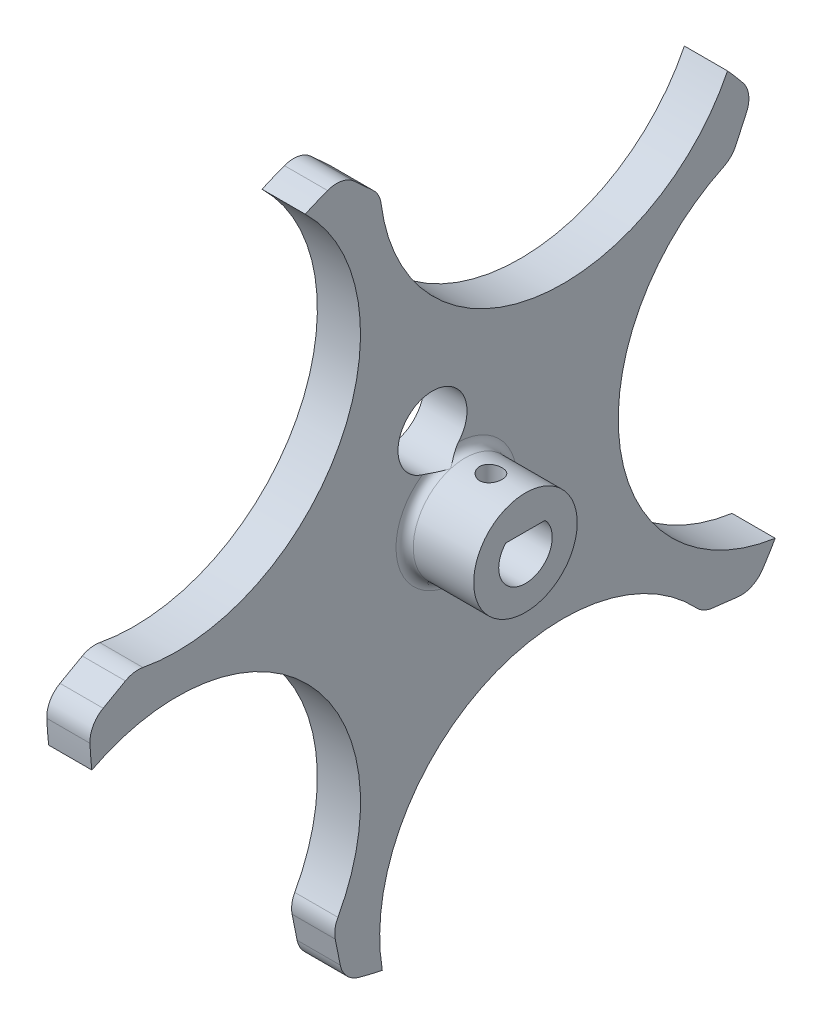
SolidWorks part; units mm, degrees
material "ABS"
ref_plane "前视基准面" through (0, 0, 0) normal (0, 0, 1) x (1, 0, 0)
ref_plane "上视基准面" through (0, 0, 0) normal (0, 1, 0) x (1, 0, 0)
ref_plane "右视基准面" through (0, 0, 0) normal (1, 0, 0) x (0, 0, -1)
ref_plane "基准面1" through (-38.0916, 0, 0) normal (-1, 0, 0) x (0, 0, 1)
sketch "草图2" plane through (-38.0916, 0, 0) normal (-1, 0, 0) x (0, 0, 1)
  line L8 (50.9114, 23.5166) -> (55.2476, 27.5126)
  line L9 (42.0845, -12.8976) -> (18.6016, -26.2672) construction
  line L10 (22.1126, 5.3045) -> (42.0845, -12.8976) construction
  line L11 (10.1802, 6.7498) -> (7.7198, 12.1087)
  line L12 (42.0845, -12.8976) -> (22.1126, 5.3045) construction
  line L13 (23.3345, -12.8976) -> (42.0845, -12.8976) construction
  line L14 (53.2241, 11.7215) -> (42.0845, -12.8976) construction
  line L15 (36.2904, 4.9347) -> (42.0845, -12.8976) construction
  line L16 (79.4441, -10.0398) -> (84.5845, -12.929)
  line L17 (42.0845, -12.8976) -> (53.2241, 11.7215) construction
  line L18 (68.941, -15.8842) -> (42.0845, -12.8976) construction
  line L19 (57.2536, -1.8766) -> (42.0845, -12.8976) construction
  line L20 (56.3471, -47.5456) -> (55.1878, -53.3272)
  line L21 (42.0845, -12.8976) -> (68.941, -15.8842) construction
  line L22 (47.5432, -39.3626) -> (42.0845, -12.8976) construction
  line L23 (57.2536, -23.9186) -> (42.0845, -12.8976) construction
  line L24 (13.5397, -37.169) -> (7.6828, -37.853)
  line L25 (42.0845, -12.8976) -> (47.5432, -39.3626) construction
  line L26 (18.6016, -26.2672) -> (42.0845, -12.8976) construction
  line L27 (36.2904, -30.7299) -> (42.0845, -12.8976) construction
  arc A41 (55.2476, 27.5126) -> (59.6047, 25.8231) centre (42.0845, -12.8976) cw
  arc A43 (7.7198, 12.1087) -> (10.673, 15.7305) centre (42.0845, -12.8976) cw
  arc A45 (10.1802, 6.7498) -> (5.1509, -33.9252) centre (2.0845, -12.8976) cw
  arc A46 (50.9114, 23.5166) -> (10.673, 15.7305) centre (29.7238, 25.1447) cw
  arc A47 (84.5845, -12.929) -> (84.3241, -17.5949) centre (42.0845, -12.8976) cw
  arc A49 (79.4441, -10.0398) -> (59.6047, 25.8231) centre (74.4452, 10.6138) cw
  arc A50 (55.1878, -53.3272) -> (50.6698, -54.5214) centre (42.0845, -12.8976) cw
  arc A52 (56.3471, -47.5456) -> (84.3241, -17.5949) centre (74.4452, -36.409) cw
  arc A53 (7.6828, -37.853) -> (5.1509, -33.9252) centre (42.0845, -12.8976) cw
  arc A55 (13.5397, -37.169) -> (50.6698, -54.5214) centre (29.7238, -50.9399) cw
  point P15 (42.0845, -12.8976)
  point P16 (42.0845, -12.8976)
  point P18 (42.0845, -12.8976)
  point P19 (42.0845, -12.8976)
  point P23 (42.0845, -12.8976)
  point P24 (42.0845, -12.8976)
  point P27 (42.0845, -12.8976)
  point P28 (42.0845, -12.8976)
  point P29 (42.0845, -12.8976)
  point P30 (42.0845, -12.8976)
  point P31 (42.0845, -12.8976)
  point P32 (42.0845, -12.8976)
  point P33 (42.0845, -12.8976)
  point P34 (42.0845, -12.8976)
  point P35 (42.0845, -12.8976)
  point P36 (42.0845, -12.8976)
  point P37 (42.0845, -12.8976)
  point P38 (42.0845, -12.8976)
  point P39 (42.0845, -12.8976)
  point P40 (42.0845, -12.8976)
  point P41 (42.0845, -12.8976)
  point P42 (42.0845, -12.8976)
  point P44 (42.0845, -12.8976)
  point P45 (42.0845, -12.8976)
  point P46 (42.0845, -12.8976)
  point P47 (42.0845, -12.8976)
  point P48 (42.0845, -12.8976)
  point P49 (42.0845, -12.8976)
  point P50 (42.0845, -12.8976)
  point P51 (42.0845, -12.8976)
  point P52 (42.0845, -12.8976)
  point P53 (42.0845, -12.8976)
  point P62 (42.0845, -12.8976)
  point P63 (42.0845, -12.8976)
  point P64 (42.0845, -12.8976)
  point P65 (42.0845, -12.8976)
  point P66 (42.0845, -12.8976)
  point P67 (42.0845, -12.8976)
  point P69 (42.0845, -12.8976)
  point P70 (42.0845, -12.8976)
  point P71 (42.0845, -12.8976)
  point P72 (42.0845, -12.8976)
  point P73 (42.0845, -12.8976)
  point P74 (42.0845, -12.8976)
  point P75 (42.0845, -12.8976)
  point P76 (42.0845, -12.8976)
  point P77 (42.0845, -12.8976)
  point P78 (42.0845, -12.8976)
  point P87 (42.0845, -12.8976)
  point P88 (42.0845, -12.8976)
  point P89 (42.0845, -12.8976)
  point P90 (42.0845, -12.8976)
  point P91 (42.0845, -12.8976)
  point P92 (42.0845, -12.8976)
  point P94 (42.0845, -12.8976)
  point P95 (42.0845, -12.8976)
  point P96 (42.0845, -12.8976)
  point P97 (42.0845, -12.8976)
  point P98 (42.0845, -12.8976)
  point P99 (42.0845, -12.8976)
  point P100 (42.0845, -12.8976)
  point P101 (42.0845, -12.8976)
  point P102 (42.0845, -12.8976)
  point P103 (42.0845, -12.8976)
  point P112 (42.0845, -12.8976)
  point P113 (42.0845, -12.8976)
  point P114 (42.0845, -12.8976)
  point P115 (42.0845, -12.8976)
  point P116 (42.0845, -12.8976)
  point P117 (42.0845, -12.8976)
  point P119 (42.0845, -12.8976)
  point P120 (42.0845, -12.8976)
  point P121 (42.0845, -12.8976)
  point P122 (42.0845, -12.8976)
  point P123 (42.0845, -12.8976)
  point P124 (42.0845, -12.8976)
  point P125 (42.0845, -12.8976)
  point P126 (42.0845, -12.8976)
  point P127 (42.0845, -12.8976)
  point P128 (42.0845, -12.8976)
  point P129 (42.0845, -12.8976)
  dimension "D1" = 5
extrude "凸台-拉伸2" add sketch "草图2" along normal mid plane 5 contours A45 L11 A43 A46 L8 A41 A49 L16 A47 A52 L20 A50 A55 L24 A53
sketch "草图4" plane through (-35.5916, 0, 0) normal (1, 0, 0) x (0, 0, -1)
  circle A0 centre (-42.0845, -12.8976) radius 6
  dimension "D1" = 12
extrude "凸台-拉伸3" add sketch "草图4" along normal blind 8
sketch "草图13" plane through (-27.5916, 0, 0) normal (1, 0, 0) x (0, 0, -1)
  line L0 (-44.3648, -10.7976) -> (-39.8041, -10.7976)
  arc A0 (-44.3648, -10.7976) -> (-39.8041, -10.7976) centre (-42.0845, -12.8976) ccw
  dimension "D1" = 6.2
  dimension "D2" = 2.1
extrude "切除-拉伸5" cut sketch "草图13" against normal blind 11.5
sketch "草图14" plane through (-40.5916, 0, 0) normal (-1, 0, 0) x (0, 0, 1)
  circle A0 centre (42.0845, -12.8976) radius 1.6
  dimension "D1" = 3.2
extrude "切除-拉伸6" cut sketch "草图14" against normal blind 12
sketch "草图15" plane through (0, -10.7976, 0) normal (0, -1, 0) x (1, 0, 0)
  line L0 (-27.5916, 36.0845) -> (-27.5916, 48.0845) construction
  circle A0 centre (-31.5916, 42.0845) radius 1.3
  dimension "D1" = 2.6
  dimension "D2" = 4
extrude "切除-拉伸7" cut sketch "草图15" against normal blind 11
fillet "圆角7" radius 1 1 edges at (-35.5916, -6.8976, 42.0845)
fillet "Fillet1" radius 3 10 edges at (-38.0916, -47.5456, 56.3471) (-38.0916, -53.3272, 55.1878) (-38.0916, -37.853, 7.6828) (-38.0916, -37.169, 13.5397) (-38.0916, 6.7498, 10.1802) (-38.0916, 12.1087, 7.7198) (-38.0916, -12.929, 84.5845) (-38.0916, -10.0398, 79.4441) (-38.0916, 27.5126, 55.2476) (-38.0916, 23.5166, 50.9114)
sketch "Sketch1" plane through (-40.5916, 0, 0) normal (-1, 0, 0) x (0, 0, 1)
  circle A15 centre (44.8569, -3.2896) radius 4
  circle A31 centre (42.0845, -12.8976) radius 1.6 construction
  dimension "D1" = 10
  dimension "D2" = 8
extrude "Cut-Extrude2" cut sketch "Sketch1" against normal blind 50
